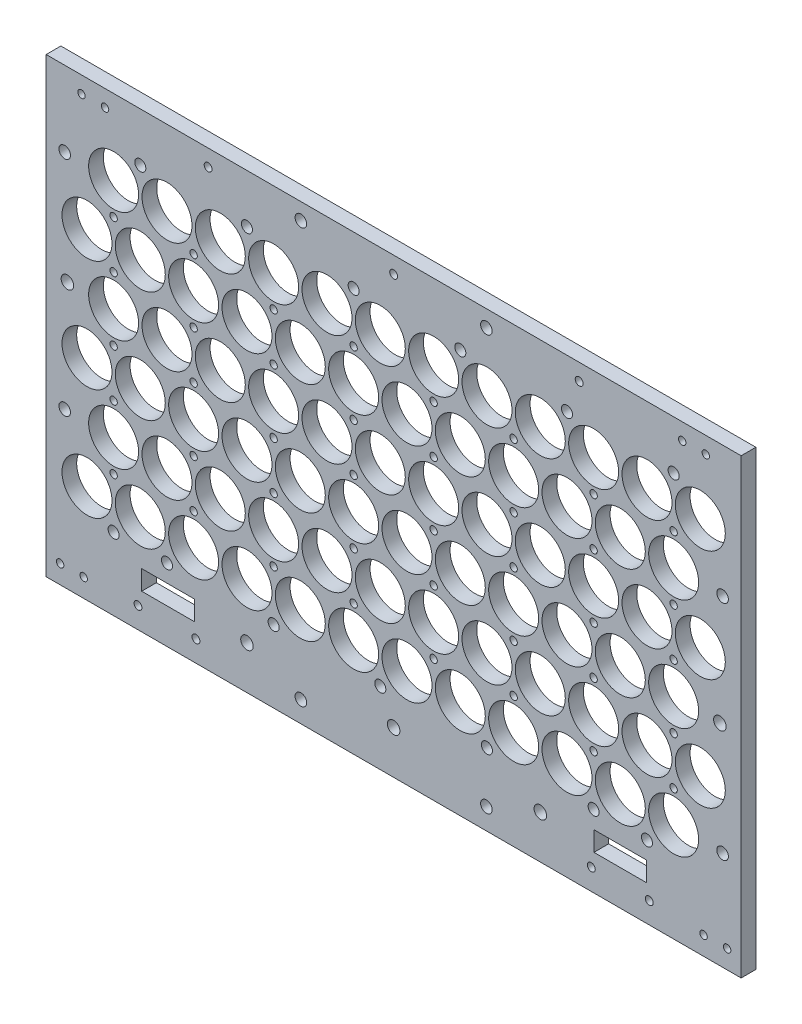
SolidWorks part; units mm, degrees
material "ABS"
ref_plane "X-Y Datum" through (0, 0, 0) normal (0, 0, 1) x (1, 0, 0)
ref_plane "X-Z Datum" through (0, 0, 0) normal (0, 1, 0) x (1, 0, 0)
ref_plane "Y-Z Datum" through (0, 0, 0) normal (1, 0, 0) x (0, 0, -1)
sketch "Sketch1" plane through (0, 0, 0) normal (0, 0, 1) x (1, 0, 0)
  line L1 (-143.025, 70.775) -> (143.025, 70.775)
  line L2 (-143.025, 70.775) -> (-143.025, -70.775)
  line L3 (-143.025, -70.775) -> (143.025, -70.775)
  line L4 (143.025, 70.775) -> (143.025, -70.775)
  line L5 (-143.025, 70.775) -> (143.025, -70.775) construction
  line L6 (-143.025, -70.775) -> (143.025, 70.775) construction
  line L13 (-149.85, -102.6) -> (149.85, -102.6)
  line L14 (-149.85, 91.65) -> (149.85, 91.65)
  line L15 (-149.85, 91.65) -> (-149.85, -102.6)
  line L16 (149.85, 91.65) -> (149.85, -102.6)
  line L17 (149.85, 70.775) -> (149.85, -70.775) construction
  line L18 (-143.025, 91.65) -> (143.025, 91.65) construction
  line L19 (-143.025, -102.6) -> (143.025, -102.6) construction
  line L20 (-149.85, 70.775) -> (-149.85, -70.775) construction
  line L21 (-132.25, -60) -> (-109.25, -60) construction
  circle A0 centre (-132.25, -60) radius 10.775
  circle A1 centre (-109.25, -60) radius 10.775 construction
  circle A2 centre (-120.75, -36) radius 10.775
  point P0 (0, 0)
  point P16 (-120.75, -60)
  dimension "D1" = 21.55
  dimension "D2" = 23
  dimension "D3" = 24
  dimension "D5" = 141.55
  dimension "D6" = 286.05
  dimension "D7" = 31.825
  dimension "D8" = 20.875
  dimension "D9" = 6.825
  dimension "D10" = 6.825
extrude "Boss-Extrude1" add sketch "Sketch1" along normal blind 6.35 contours A0 L3 L4 L1 L2 A2 | A2 | A0 | A0 L2 L3 | L1 L4 L3 L2 region at (2.4105, 0.9241, 0) region at (-140.6182, -68.3682, 0) region at (-132.25, -60, 0) region at (-146.2785, -5.475, 0) region at (-120.75, -36, 0)
sketch "Sketch3" plane through (0, 0, 6.35) normal (0, 0, 1) x (1, 0, 0)
  line L4 (143.025, 70.775) -> (-143.025, 70.775)
  line L5 (143.025, -70.775) -> (143.025, 70.775)
  line L6 (-143.025, -70.775) -> (143.025, -70.775)
  line L7 (-143.025, 70.775) -> (-143.025, -70.775)
  line L8 (143.025, 70.775) -> (-143.025, 70.775)
  line L9 (143.025, -70.775) -> (143.025, 70.775)
  line L10 (-143.025, -70.775) -> (143.025, -70.775)
  line L11 (-143.025, 70.775) -> (-143.025, -70.775)
  circle A1 centre (-120.75, -36) radius 10.775
  circle A2 centre (-120.75, -36) radius 10.775
  circle A3 centre (-132.25, -60) radius 10.775
  circle A4 centre (-132.25, -60) radius 10.775
  dimension "D1" = 0
  dimension "D2" = 0
  dimension "D3" = 0
extrude "Cut-Extrude1" cut sketch "Sketch3" against normal through all contours A4 region at (-132.25, -60, 6.35)
sketch "Sketch4" plane through (0, 0, 6.35) normal (0, 0, 1) x (1, 0, 0)
  line L4 (143.025, 70.775) -> (-143.025, 70.775)
  line L5 (143.025, -70.775) -> (143.025, 70.775)
  line L6 (-143.025, -70.775) -> (143.025, -70.775)
  line L7 (-143.025, 70.775) -> (-143.025, -70.775)
  line L8 (143.025, 70.775) -> (-143.025, 70.775)
  line L9 (143.025, -70.775) -> (143.025, 70.775)
  line L10 (-143.025, -70.775) -> (143.025, -70.775)
  line L11 (-143.025, 70.775) -> (-143.025, -70.775)
  circle A1 centre (-120.75, -36) radius 10.775
  circle A2 centre (-120.75, -36) radius 10.775
  circle A3 centre (-132.25, -60) radius 10.775
  circle A4 centre (-132.25, -60) radius 10.775
  dimension "D1" = 0
  dimension "D2" = 0
  dimension "D3" = 0
extrude "Cut-Extrude2" cut sketch "Sketch4" against normal through all contours A2 region at (-120.75, -36, 6.35)
pattern_linear "LPattern1" count 12 spacing 23 along (1, 0, 0) of "Cut-Extrude1", "Cut-Extrude2"
pattern_linear "LPattern2" count 3 spacing 48 along (0, 1, 0) of "LPattern1"
sketch "Sketch5" plane through (0, 0, 6.35) normal (0, 0, 1) x (1, 0, 0)
  line L4 (105.3154, -79.3475) -> (90.1846, -79.3475)
  line L5 (90.37, -80.3) -> (90.37, -83.4115)
  line L6 (90.37, -83.4115) -> (105.13, -83.4115)
  line L7 (105.13, -83.4115) -> (105.13, -80.3)
  line L8 (105.3154, -79.3475) -> (90.1846, -79.3475)
  line L9 (90.37, -80.3) -> (90.37, -83.4115)
  line L10 (90.37, -83.4115) -> (105.13, -83.4115)
  line L11 (105.13, -83.4115) -> (105.13, -80.3)
  line L12 (-108.668, -78.95) -> (-108.668, -87.4115)
  line L13 (-108.668, -87.4115) -> (-85.908, -87.4115)
  line L14 (-85.908, -87.4115) -> (-85.908, -78.95)
  line L15 (86.37, -78.95) -> (86.37, -87.4115)
  line L16 (-89.7226, -79.3475) -> (-104.8534, -79.3475)
  line L17 (-104.668, -80.3) -> (-104.668, -83.4115)
  line L18 (-104.668, -83.4115) -> (-89.908, -83.4115)
  line L19 (-89.908, -83.4115) -> (-89.908, -80.3)
  line L20 (-89.7226, -79.3475) -> (-104.8534, -79.3475)
  line L21 (-104.668, -80.3) -> (-104.668, -83.4115)
  line L22 (-104.668, -83.4115) -> (-89.908, -83.4115)
  line L23 (-89.908, -83.4115) -> (-89.908, -80.3)
  line L24 (86.37, -87.4115) -> (109.13, -87.4115)
  line L25 (109.13, -87.4115) -> (109.13, -78.95)
  line L26 (149.85, -78.95) -> (-149.85, -78.95) construction
  line L27 (149.85, -78.95) -> (-149.85, -78.95)
  line L28 (109.13, -87.4115) -> (109.13, -80.3) construction
  line L29 (86.37, -80.3) -> (86.37, -87.4115) construction
  line L30 (-85.908, -87.4115) -> (-85.908, -80.3) construction
  line L31 (-108.668, -80.3) -> (-108.668, -87.4115) construction
  arc A2 (90.37, -80.3) -> (90.1846, -79.3475) centre (87.83, -80.3) ccw
  arc A3 (105.3154, -79.3475) -> (105.13, -80.3) centre (107.67, -80.3) ccw
  arc A4 (90.37, -80.3) -> (90.1846, -79.3475) centre (87.83, -80.3) ccw
  arc A5 (105.3154, -79.3475) -> (105.13, -80.3) centre (107.67, -80.3) ccw
  arc A8 (-104.668, -80.3) -> (-104.8534, -79.3475) centre (-107.208, -80.3) ccw
  arc A9 (-89.7226, -79.3475) -> (-89.908, -80.3) centre (-87.368, -80.3) ccw
  arc A10 (-104.668, -80.3) -> (-104.8534, -79.3475) centre (-107.208, -80.3) ccw
  arc A11 (-89.7226, -79.3475) -> (-89.908, -80.3) centre (-87.368, -80.3) ccw
  dimension "D1" = 0
  dimension "D2" = 0
  dimension "D3" = 4
extrude "Cut-Extrude3" cut sketch "Sketch5" against normal through all contours L25 L27 L15 L24 L8 A5 L11 L10 L9 A4 | A5 L8 A4 L9 L10 L11 | L14 L27 L12 L13 L20 A11 L23 L22 L21 A10 | A11 L20 A10 L21 L22 L23 region at (97.75, -81.376, 6.35) region at (-97.288, -83.9995, 6.35) region at (97.75, -83.9995, 6.35) region at (-97.288, -81.376, 6.35)
sketch "Sketch7" plane through (0, 0, 6.35) normal (0, 0, 1) x (1, 0, 0)
  line L0 (0, -3.4925) -> (0, 3.4925) construction
  point P0 (0, 85.3)
  point P1 (80, 85.3)
  point P3 (-124.45, 85.3)
  point P5 (-134.61, 85.3)
  point P7 (-133.6575, -94.6)
  point P9 (-143.8175, -94.6)
  point P11 (133.6575, -94.6)
  point P13 (143.8175, -94.6)
  point P17 (124.45, 85.3)
  point P19 (134.61, 85.3)
  point P21 (110.25, -93.5057)
  point P23 (85.25, -93.5057)
  point P28 (-80, 85.3)
  point P29 (-110.25, -93.5057)
  point P31 (-85.25, -93.5057)
hole_wizard "M3 Clearance Hole1" positions "Sketch8" profile "Sketch9" hole size "M3" standard "ANSI Metric" end condition through all
sketch "Sketch8" plane through (0, 0, 6.35) normal (0, 0, 1) x (1, 0, 0)
  point P3 (124.45, 85.3)
  point P6 (134.61, 85.3)
  point P12 (-124.45, 85.3)
  point P15 (-134.61, 85.3)
  point P18 (-143.8175, -94.6)
  point P21 (-133.6575, -94.6)
  point P24 (133.6575, -94.6)
  point P27 (143.8175, -94.6)
sketch "Sketch9" plane through (124.45, 85.3, 6.35) normal (1, 0, 0) x (0, -1, 0)
  line L0 (0, 0) -> (0, 6.35)
  line L1 (0, 6.35) -> (1.6, 6.35)
  line L2 (1.6, 6.35) -> (1.6, 0)
  line L5 (1.6, 0) -> (0, 0)
  line L11 (0, -6.35) -> (0, 107.95) construction
  dimension "Thru Hole Dia." = 3.2
  dimension "Thru Hole Depth" = 6.35
hole_wizard "M3 Clearance Hole2" positions "Sketch12" profile "Sketch13" hole size "M3" standard "ANSI Metric" end condition through all
sketch "Sketch12" plane through (0, 0, 6.35) normal (0, 0, 1) x (1, 0, 0)
  point P0 (110.25, -93.5057)
  point P3 (85.25, -93.5057)
  point P6 (-80, 85.3)
  point P9 (0, 85.3)
  point P12 (80, 85.3)
  point P16 (-85.25, -93.5057)
  point P19 (-110.25, -93.5057)
sketch "Sketch13" plane through (110.25, -93.5057, 6.35) normal (1, 0, 0) x (0, -1, 0)
  line L0 (0, 0) -> (0, 6.35)
  line L1 (0, 6.35) -> (1.7, 6.35)
  line L2 (1.7, 6.35) -> (1.7, 0)
  line L5 (1.7, 0) -> (0, 0)
  line L11 (0, -6.35) -> (0, 107.95) construction
  dimension "Thru Hole Dia." = 3.4
  dimension "Thru Hole Depth" = 6.35
sketch "Sketch14" plane through (0, 0, 6.35) normal (0, 0, 1) x (1, 0, 0)
  line L0 (131.525, -12) -> (149.85, -12) construction
  line L1 (149.85, 91.65) -> (149.85, -102.6) construction
  line L2 (-131.525, 12) -> (-149.85, 12) construction
  line L3 (-149.85, 91.65) -> (-149.85, -102.6) construction
  line L4 (149.85, -78.95) -> (-149.85, -78.95) construction
  line L5 (149.85, -78.95) -> (-149.85, -78.95) construction
  line L6 (149.85, -83.95) -> (-149.85, -83.95) construction
  line L7 (68.55, -70.9014) -> (57.95, -70.9014) construction
  line L8 (68.55, -67.0427) -> (68.55, -74.76) construction
  line L9 (57.95, -67.0427) -> (57.95, -74.76) construction
  line L10 (63.25, -70.9014) -> (63.25, -83.95) construction
  line L18 (0, -3.4925) -> (0, 3.4925) construction
  circle A0 centre (120.75, -12) radius 10.775 construction
  circle A1 centre (-120.75, 12) radius 10.775 construction
  circle A2 centre (140.6875, -12) radius 2.7
  circle A3 centre (-140.6875, 12) radius 2.7
  circle A4 centre (63.25, -83.95) radius 2.7
  circle A6 centre (-63.25, -83.95) radius 2.7
  circle A8 centre (0, -83.95) radius 2.7
  dimension "D1" = 5.4
  dimension "D3" = 5.4
  dimension "D2" = 5
extrude "Cut-Extrude4" cut sketch "Sketch14" against normal through all
sketch "Sketch15" plane through (0, 0, 6.35) normal (0, 0, 1) x (1, 0, 0)
  line L0 (-6.35, 85.3) -> (86.35, 85.3) construction
  line L1 (-6.35, 90.65) -> (-6.35, 79.95) construction
  line L2 (86.35, 79.95) -> (86.35, 90.65) construction
  line L3 (-86.35, 85.3) -> (6.35, 85.3) construction
  line L4 (-86.35, 90.65) -> (-86.35, 79.95) construction
  line L5 (6.35, 79.95) -> (6.35, 90.65) construction
  line L6 (131.525, 36) -> (149.85, 36) construction
  line L7 (149.85, 94.825) -> (149.85, -105.775) construction
  line L8 (131.525, -60) -> (149.85, -60) construction
  line L9 (-131.525, -36) -> (-149.85, -36) construction
  line L10 (-149.85, -105.775) -> (-149.85, 94.825) construction
  line L11 (-131.525, 60) -> (-149.85, 60) construction
  line L12 (-40, 85.3) -> (-40, -102.6) construction
  line L13 (-149.85, -102.6) -> (149.85, -102.6) construction
  line L14 (40, 85.3) -> (40, -102.6) construction
  line L16 (85.25, -93.5057) -> (-85.25, -93.5057) construction
  circle A0 centre (-40, 85.3) radius 2.5
  circle A1 centre (40, 85.3) radius 2.5
  circle A2 centre (120.75, 36) radius 10.775 construction
  circle A3 centre (120.75, -60) radius 10.775 construction
  circle A4 centre (141.85, 36) radius 2.5
  circle A5 centre (141.85, -60) radius 2.5
  circle A6 centre (-120.75, -36) radius 10.775 construction
  circle A7 centre (-120.75, 60) radius 10.775 construction
  circle A8 centre (-141.85, -36) radius 2.5
  circle A9 centre (-141.85, 60) radius 2.5
  circle A10 centre (-40, -93.5057) radius 2.5
  circle A11 centre (40, -93.5057) radius 2.5
  point P60 (0, 0)
  point P61 (146.1361, -60)
  point P62 (0, 0)
  point P63 (146.3746, 36)
  point P64 (0, 0)
  point P65 (0, 0)
  point P66 (0, 0)
  point P67 (0, 0)
  point P68 (0, 0)
  dimension "D1" = 5
  dimension "D2" = 8
  dimension "D3" = 8
  dimension "D4" = 8
  dimension "D5" = 8
extrude "Cut-Extrude5" cut sketch "Sketch15" against normal through all
sketch "Sketch16" plane through (0, 0, 6.35) normal (0, 0, 1) x (1, 0, 0)
  circle A0 centre (86.25, 46.29) radius 1.1906 construction
  circle A1 centre (120.75, 49.71) radius 1.1906 construction
  circle A2 centre (86.25, 25.71) radius 1.1906 construction
  circle A3 centre (120.75, 22.29) radius 1.1906 construction
  circle A4 centre (86.25, -1.71) radius 1.1906 construction
  circle A5 centre (120.75, 1.71) radius 1.1906 construction
  circle A6 centre (86.25, -22.29) radius 1.1906 construction
  circle A7 centre (120.75, -25.71) radius 1.1906 construction
  circle A8 centre (86.25, -49.71) radius 1.1906 construction
  circle A9 centre (120.75, -46.29) radius 1.1906 construction
  circle A10 centre (86.25, 46.29) radius 1.1906 construction
  circle A11 centre (120.75, 49.71) radius 1.1906 construction
  circle A12 centre (86.25, 25.71) radius 1.1906 construction
  circle A13 centre (120.75, 22.29) radius 1.1906 construction
  circle A14 centre (86.25, -1.71) radius 1.1906 construction
  circle A15 centre (120.75, 1.71) radius 1.1906 construction
  circle A16 centre (86.25, -22.29) radius 1.1906 construction
  circle A17 centre (120.75, -25.71) radius 1.1906 construction
  circle A18 centre (86.25, -49.71) radius 1.1906 construction
  circle A19 centre (120.75, -46.29) radius 1.1906 construction
  circle A20 centre (86.25, -49.71) radius 1.5875
  circle A21 centre (120.75, -46.29) radius 1.5875
  circle A22 centre (120.75, -25.71) radius 1.5875
  circle A23 centre (86.25, -22.29) radius 1.5875
  circle A24 centre (120.75, 1.71) radius 1.5875
  circle A25 centre (86.25, -1.71) radius 1.5875
  circle A26 centre (120.75, 22.29) radius 1.5875
  circle A27 centre (86.25, 25.71) radius 1.5875
  circle A28 centre (120.75, 49.71) radius 1.5875
  circle A29 centre (86.25, 46.29) radius 1.5875
  dimension "D1" = 3.175
extrude "Cut-Extrude6" cut sketch "Sketch16" against normal through all
pattern_linear "LPattern3" count 4 spacing 69 along (-1, 0, 0) of "Cut-Extrude6"
sketch "Sketch18" plane through (0, 0, 6.35) normal (0, 0, 1) x (1, 0, 0)
  circle A0 centre (-120.75, -71.41) radius 1.5875 construction
  circle A1 centre (-97.75, -71.41) radius 1.5875 construction
  circle A2 centre (-51.75, -71.41) radius 1.5875 construction
  circle A3 centre (-5.75, -71.41) radius 1.5875 construction
  circle A4 centre (40.25, -71.41) radius 1.5875 construction
  circle A5 centre (-109.25, 71.41) radius 1.5875 construction
  circle A6 centre (-63.25, 71.41) radius 1.5875 construction
  circle A7 centre (-17.25, 71.41) radius 1.5875 construction
  circle A8 centre (28.75, 71.41) radius 1.5875 construction
  circle A9 centre (74.75, 71.41) radius 1.5875 construction
  circle A10 centre (120.75, 71.41) radius 1.5875 construction
  circle A11 centre (86.25, -71.41) radius 1.5875 construction
  circle A12 centre (109.25, -71.41) radius 1.5875 construction
  circle A13 centre (-120.75, -71.41) radius 1.5875 construction
  circle A14 centre (-97.75, -71.41) radius 1.5875 construction
  circle A15 centre (-51.75, -71.41) radius 1.5875 construction
  circle A16 centre (-5.75, -71.41) radius 1.5875 construction
  circle A17 centre (40.25, -71.41) radius 1.5875 construction
  circle A18 centre (-109.25, 71.41) radius 1.5875 construction
  circle A19 centre (-63.25, 71.41) radius 1.5875 construction
  circle A20 centre (-17.25, 71.41) radius 1.5875 construction
  circle A21 centre (28.75, 71.41) radius 1.5875 construction
  circle A22 centre (74.75, 71.41) radius 1.5875 construction
  circle A23 centre (120.75, 71.41) radius 1.5875 construction
  circle A24 centre (86.25, -71.41) radius 1.5875 construction
  circle A25 centre (109.25, -71.41) radius 1.5875 construction
  circle A26 centre (109.25, -71.41) radius 2.3813
  circle A27 centre (86.25, -71.41) radius 2.3813
  circle A28 centre (120.75, 71.41) radius 2.3813
  circle A29 centre (74.75, 71.41) radius 2.3813
  circle A30 centre (28.75, 71.41) radius 2.3813
  circle A31 centre (-17.25, 71.41) radius 2.3812
  circle A32 centre (-63.25, 71.41) radius 2.3812
  circle A33 centre (-109.25, 71.41) radius 2.3813
  circle A34 centre (40.25, -71.41) radius 2.3812
  circle A35 centre (-5.75, -71.41) radius 2.3812
  circle A36 centre (-51.75, -71.41) radius 2.3812
  circle A37 centre (-97.75, -71.41) radius 2.3813
  circle A38 centre (-120.75, -71.41) radius 2.3813
  dimension "D1" = 4.7625
extrude "Cut-Extrude7" cut sketch "Sketch18" against normal through all
sketch "Sketch19" plane through (0, 91.65, 0) normal (0, 1, 0) x (1, 0, 0)
  line L4 (149.85, 0) -> (-149.85, 0)
  line L5 (-149.85, 0) -> (-149.85, -6.35)
  line L6 (-149.85, -6.35) -> (149.85, -6.35)
  line L7 (149.85, -6.35) -> (149.85, 0)
  line L8 (149.85, 0) -> (-149.85, 0)
  line L9 (-149.85, 0) -> (-149.85, -6.35)
  line L10 (-149.85, -6.35) -> (149.85, -6.35)
  line L11 (149.85, -6.35) -> (149.85, 0)
  dimension "D1" = 0
extrude "Boss-Extrude2" add sketch "Sketch19" along normal blind 0.7937
